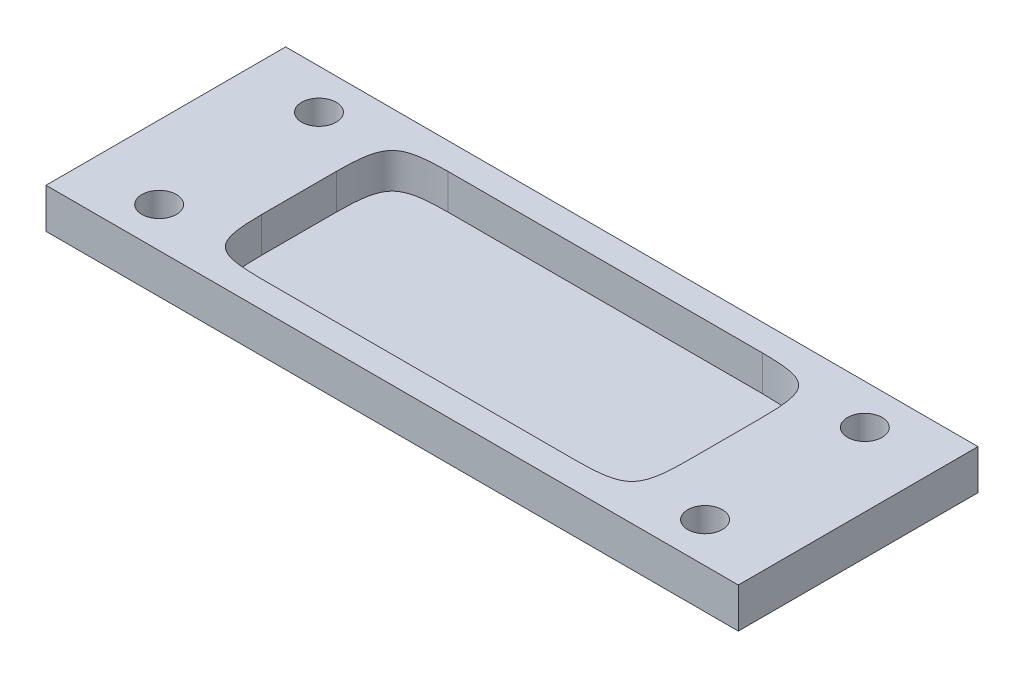
SolidWorks part; units mm, degrees
ref_plane "Front Plane" through (0, 0, 0) normal (0, 0, 1) x (1, 0, 0)
ref_plane "Top Plane" through (0, 0, 0) normal (0, 1, 0) x (1, 0, 0)
ref_plane "Right Plane" through (0, 0, 0) normal (1, 0, 0) x (0, 0, -1)
sketch "Sketch1" plane through (0, 0, 0) normal (0, 1, 0) x (1, 0, 0)
  line L1 (-26, 9) -> (26, 9)
  line L2 (-26, 9) -> (-26, -9)
  line L3 (-26, -9) -> (26, -9)
  line L4 (26, 9) -> (26, -9)
  line L5 (-26, 9) -> (26, -9) construction
  line L6 (-26, -9) -> (26, 9) construction
  point P0 (0, 0)
  dimension "D1" = 52
  dimension "D2" = 18
extrude "Boss-Extrude1" add sketch "Sketch1" along normal blind 3
sketch "Sketch2" plane through (0, 3, 0) normal (0, 1, 0) x (1, 0, 0)
  line L1 (-16, 7) -> (16, 7)
  line L2 (-16, 7) -> (-16, -7)
  line L3 (-16, -7) -> (16, -7)
  line L4 (16, 7) -> (16, -7)
  line L5 (-16, 7) -> (16, -7) construction
  line L6 (-16, -7) -> (16, 7) construction
  point P0 (0, 0)
  dimension "D1" = 32
  dimension "D2" = 14
extrude "Cut-Extrude1" cut sketch "Sketch2" against normal blind 2.65
fillet "Fillet1" radius 4.2 4 edges at (16, 1.675, 7) (-16, 1.675, 7) (-16, 1.675, -7) (16, 1.675, -7) conic rho 0.65
hole_wizard "Ø2.6 (2.6) Diameter Hole1" positions "Sketch3" profile "Sketch5" hole size "Ø2.6" standard "ANSI Metric" end condition through all
sketch "Sketch3" plane through (0, 3, 0) normal (0, 1, 0) x (1, 0, 0)
  line L0 (-26, -9) -> (26, -9) construction
  line L1 (-26, 9) -> (-26, -9) construction
  point P0 (-20.5, 6)
  point P2 (-20.5, -6)
  point P4 (20.5, 6)
  point P6 (20.5, -6)
  dimension "D1" = 41
  dimension "D2" = 12
  dimension "D3" = 3
  dimension "D4" = 5.5
sketch "Sketch5" plane through (-20.5, 3, -6) normal (1, 0, 0) x (0, 0, 1)
  line L0 (0, 0) -> (0, 3)
  line L1 (0, 3) -> (1.3, 3)
  line L2 (1.3, 3) -> (1.3, 0)
  line L5 (1.3, 0) -> (0, 0)
  line L11 (0, -6.35) -> (0, 107.95) construction
  dimension "Thru Hole Dia." = 2.6
  dimension "Thru Hole Depth" = 3
